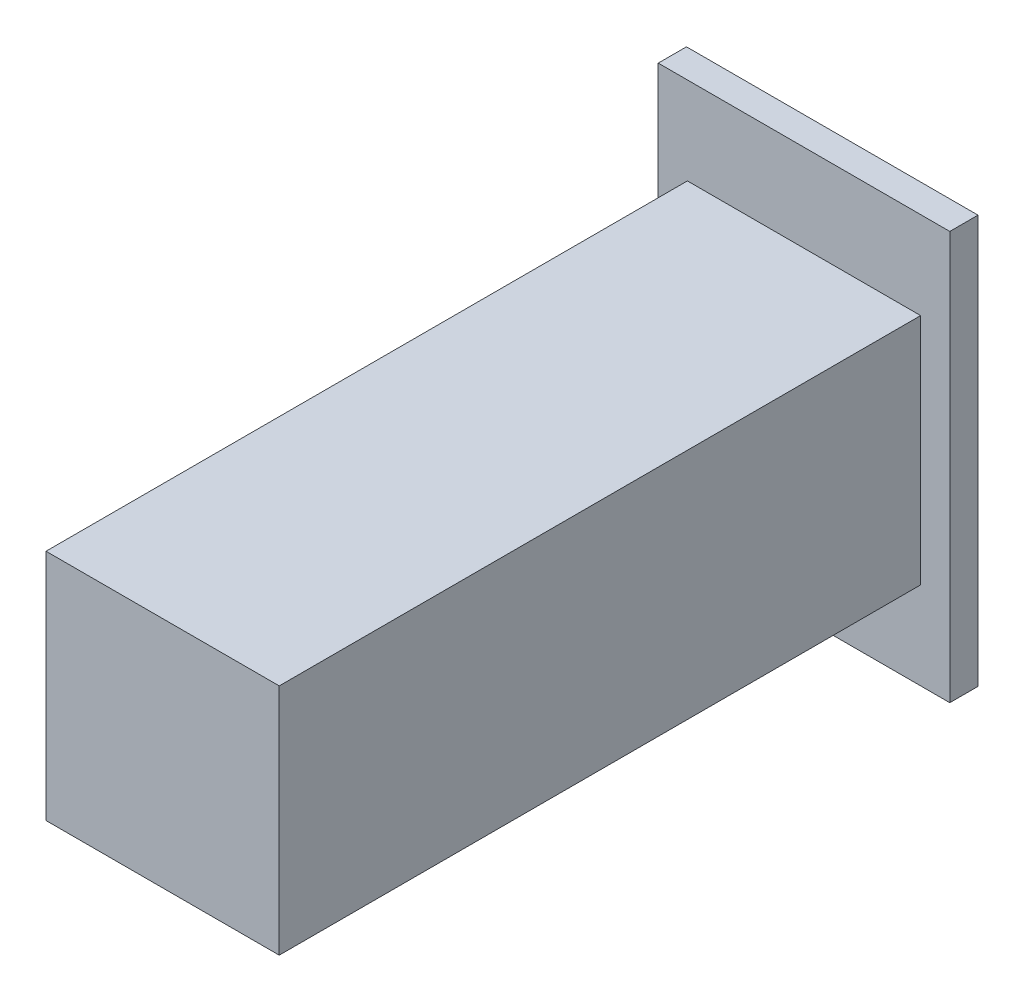
SolidWorks part; units mm, degrees
ref_plane "Front Plane" through (0, 0, 0) normal (0, 0, 1) x (1, 0, 0)
ref_plane "Top Plane" through (0, 0, 0) normal (0, 1, 0) x (1, 0, 0)
ref_plane "Right Plane" through (0, 0, 0) normal (1, 0, 0) x (0, 0, -1)
sketch "Sketch1" plane through (0, 0, 0) normal (0, 0, 1) x (1, 0, 0)
  line L1 (12.5, -17.5) -> (-12.5, -17.5)
  line L2 (12.5, -17.5) -> (12.5, 17.5)
  line L3 (12.5, 17.5) -> (-12.5, 17.5)
  line L4 (-12.5, -17.5) -> (-12.5, 17.5)
  line L5 (12.5, -17.5) -> (-12.5, 17.5) construction
  line L6 (12.5, 17.5) -> (-12.5, -17.5) construction
  line L7 (10, -10) -> (-10, -10)
  line L8 (10, -10) -> (10, 10)
  line L9 (10, 10) -> (-10, 10)
  line L10 (-10, -10) -> (-10, 10)
  line L11 (10, -10) -> (-10, 10) construction
  line L12 (10, 10) -> (-10, -10) construction
  point P0 (0, 0)
  point P6 (0, 0)
  dimension "D1" = 25
  dimension "D2" = 35
  dimension "D3" = 20
  dimension "D4" = 20
extrude "Boss-Extrude1" add sketch "Sketch1" along normal blind 2.42
extrude "Boss-Extrude2" add sketch "Sketch1<2>" along normal blind 57.42 contours L10 L7 L8 L9 region at (0, 0, 0)
sketch "Sketch1<2>" plane through (0, 0, 0) normal (0, 0, 1) x (1, 0, 0) same geometry as "Sketch1"
